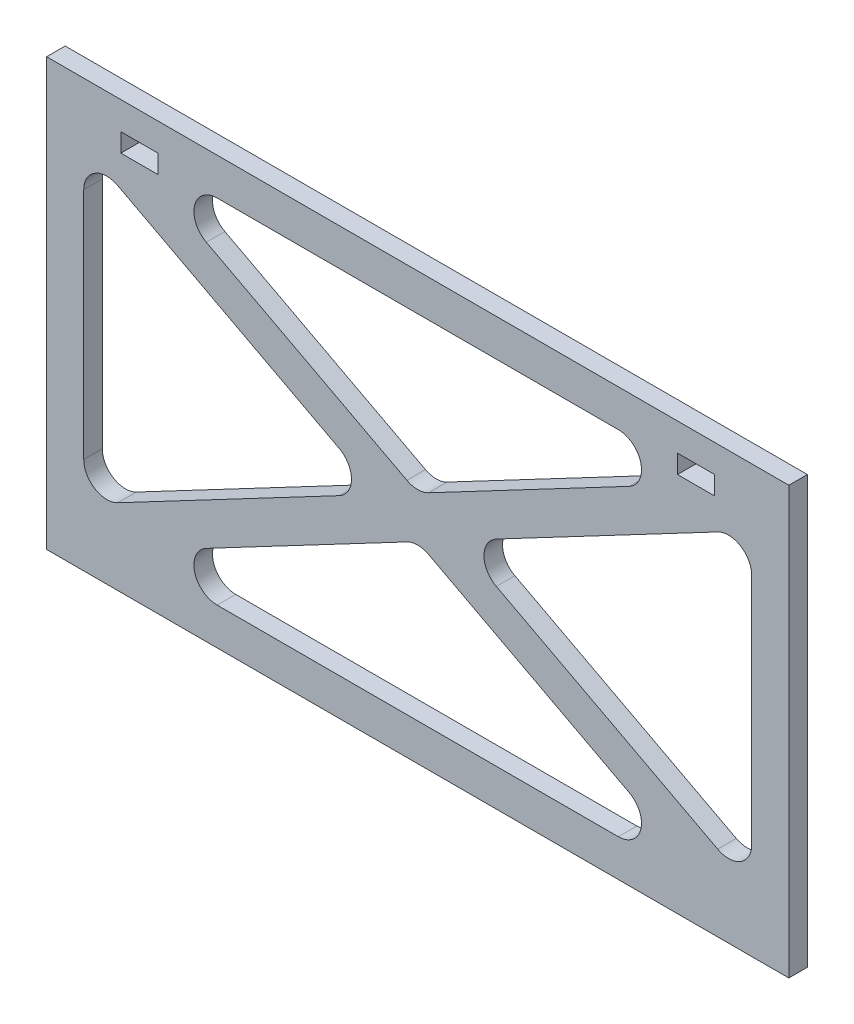
SolidWorks part; units mm, degrees
material "Beech"
ref_plane "Front Plane" through (0, 0, 0) normal (0, 0, 1) x (1, 0, 0)
ref_plane "Top Plane" through (0, 0, 0) normal (0, 1, 0) x (1, 0, 0)
ref_plane "Right Plane" through (0, 0, 0) normal (1, 0, 0) x (0, 0, -1)
sketch "Sketch1" plane through (0, 0, 0) normal (0, 0, 1) x (1, 0, 0)
  line L0 (91.44, 48.26) -> (-91.44, 48.26)
  line L1 (101.6, 58.42) -> (-101.6, 58.42)
  line L2 (101.6, 58.42) -> (101.6, -58.42)
  line L3 (101.6, -58.42) -> (-101.6, -58.42)
  line L4 (-101.6, 58.42) -> (-101.6, -58.42)
  line L5 (101.6, 58.42) -> (-101.6, -58.42) construction
  line L6 (101.6, -58.42) -> (-101.6, 58.42) construction
  line L7 (-91.44, 48.26) -> (-91.44, -48.26)
  line L8 (91.44, -48.26) -> (-91.44, -48.26)
  line L9 (91.44, 48.26) -> (91.44, -48.26)
  line L10 (-91.44, 48.26) -> (91.44, -48.26) construction
  line L11 (-91.44, -48.26) -> (91.44, 48.26) construction
  line L12 (-93.8111, 43.7673) -> (89.0689, -52.7527)
  line L13 (-89.0689, -52.7527) -> (93.8111, 43.7673)
  line L14 (-89.0689, 52.7527) -> (93.8111, -43.7673)
  line L15 (-93.8111, -43.7673) -> (89.0689, 52.7527)
  line L16 (0, 0) -> (0, 58.42) construction
  point P0 (0, 0)
  dimension "D1" = 116.84
  dimension "D2" = 203.2
  dimension "D3" = 10.16
  dimension "D4" = 5.08
  dimension "D5" = 5.08
extrude "Boss-Extrude1" add sketch "Sketch1" along normal blind 5.08 contours L1 L4 L3 L2 L0 L9 L8 L7 | L12 L15 L14 L0 L7 | L15 L14 L13 L9 L0 | L15 L12 L13 L14 | L15 L7 L8 L13 L12 | L14 L13 L12 L8 L9 | L14 L0 | L15 L0 region at (47.0953, 24.8558, 0) region at (-47.0953, 24.8558, 0) region at (0, 0, 0) region at (47.0953, -24.8558, 0) region at (-47.0953, -24.8558, 0) region at (99.256, 0, 0)
fillet "Fillet1" radius 6.35 12 edges at (10.8836, 0, 2.54) (91.44, -42.5159, 2.54) (80.5564, -48.26, 2.54) (-80.5564, -48.26, 2.54) (91.44, 42.5159, 2.54) (80.5564, 48.26, 2.54) (-80.5564, 48.26, 2.54) (0, -5.7441, 2.54) (-10.8836, 0, 2.54) (0, 5.7441, 2.54) (-91.44, -42.5159, 2.54) (-91.44, 42.5159, 2.54)
sketch "Sketch2" plane through (0, 0, 5.08) normal (0, 0, 1) x (1, 0, 0)
  line L0 (-81.28, 50.8) -> (-71.12, 50.8)
  line L1 (-81.28, 50.8) -> (-81.28, 45.72)
  line L2 (-81.28, 45.72) -> (-71.12, 45.72)
  line L3 (-71.12, 50.8) -> (-71.12, 45.72)
  line L4 (-81.28, 50.8) -> (-71.12, 45.72) construction
  line L5 (-81.28, 45.72) -> (-71.12, 50.8) construction
  line L6 (-101.6, 58.42) -> (-101.6, -58.42) construction
  line L7 (101.6, 58.42) -> (-101.6, 58.42) construction
  line L8 (0, 0) -> (0, 58.42) construction
  line L9 (81.28, 45.72) -> (71.12, 50.8) construction
  line L10 (81.28, 50.8) -> (71.12, 45.72) construction
  line L11 (71.12, 50.8) -> (71.12, 45.72)
  line L12 (81.28, 45.72) -> (71.12, 45.72)
  line L13 (81.28, 50.8) -> (81.28, 45.72)
  line L14 (81.28, 50.8) -> (71.12, 50.8)
  point P4 (-76.2, 48.26)
  point P16 (76.2, 48.26)
  dimension "D1" = 25.4
  dimension "D2" = 10.16
  dimension "D3" = 10.16
  dimension "D4" = 5.08
extrude "Cut-Extrude1" cut sketch "Sketch2" against normal through all both and the other way through all
